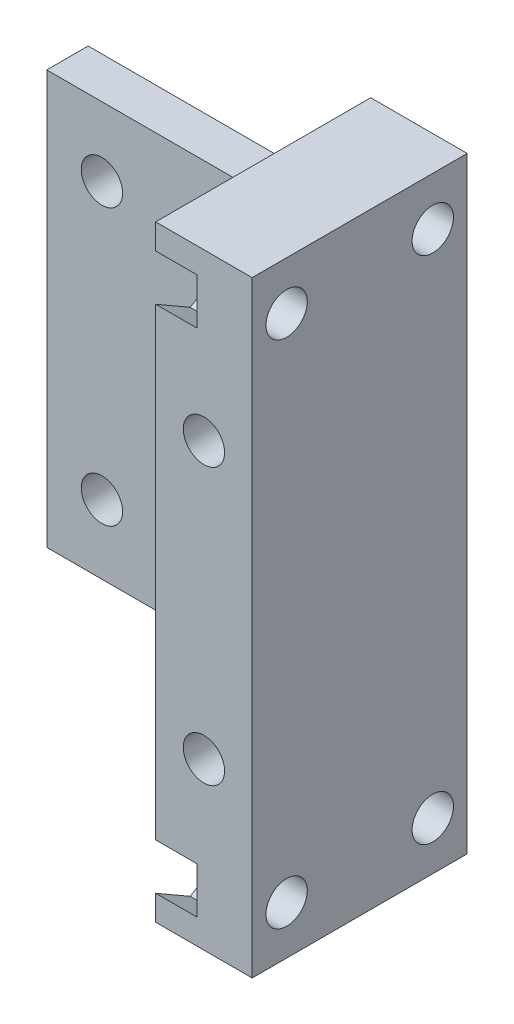
SolidWorks part; units mm, degrees
ref_plane "Front Plane" through (0, 0, 0) normal (0, 0, 1) x (1, 0, 0)
ref_plane "Top Plane" through (0, 0, 0) normal (0, 1, 0) x (1, 0, 0)
ref_plane "Right Plane" through (0, 0, 0) normal (1, 0, 0) x (0, 0, -1)
sketch "Sketch1" plane through (0, 0, 0) normal (0, 0, 1) x (1, 0, 0)
  line L1 (373.5029, -313.2952) -> (346.0029, -313.2952)
  line L2 (373.5029, -313.2952) -> (373.5029, -343.2952)
  line L3 (373.5029, -343.2952) -> (346.0029, -343.2952)
  line L4 (346.0029, -313.2952) -> (346.0029, -343.2952)
  line L8 (373.5029, -313.2952) -> (366.5029, -313.2952)
  line L9 (373.5029, -313.2952) -> (373.5029, -343.2952)
  line L10 (373.5029, -343.2952) -> (366.5029, -343.2952)
  line L11 (366.5029, -313.2952) -> (366.5029, -343.2952)
  circle A1 centre (370.0029, -338.2952) radius 1.5
  circle A2 centre (370.0029, -318.2952) radius 1.5
  circle A4 centre (350.0029, -318.2952) radius 1.5
  circle A5 centre (350.0029, -338.2952) radius 1.5
  point P4 (0, 0)
  point P5 (0, 0)
  point P6 (0, 0)
  point P7 (0, 0)
  point P8 (0, 0)
  point P9 (0, 0)
  point P10 (0, 0)
  point P11 (373.5029, -313.2952)
  point P16 (0, 0)
  dimension "D4" = 3
  dimension "D5" = 3
  dimension "D6" = 3
  dimension "D7" = 3
  dimension "D8" = 20
  dimension "D9" = 20
  dimension "D10" = 20
  dimension "D2" = 5
  dimension "D3" = 7
  dimension "D12" = 5
  dimension "D13" = 4
  dimension "D14" = 3.5
extrude "Boss-Extrude1" add sketch "Sketch1" along normal blind 5 contours L1 L11 L3 L2 A2 A1 | L11 L1 L4 L3 region at (370.0029, -328.2952, 0) region at (356.4, -328.2952, 0)
extrude "Boss-Extrude2" add sketch "Sketch1<3>" along normal blind 15.6 contours L1 L11 L3 L2 A2 A1 region at (370.0029, -328.2952, 0)
sketch "Sketch1<3>" plane through (0, 0, 0) normal (0, 0, 1) x (1, 0, 0) same geometry as "Sketch1"
sketch "Sketch4" plane through (373.5029, 0, 0) normal (1, 0, 0) x (0, 0, -1)
  line L0 (-15.6, -328.2952) -> (0, -328.2952) construction
  line L1 (-15.6, -313.2952) -> (0, -313.2952)
  line L2 (-15.6, -313.2952) -> (-15.6, -306.2952)
  line L3 (-15.6, -306.2952) -> (0, -306.2952)
  line L5 (-15.6, -313.2952) -> (0, -306.2952) construction
  line L6 (-15.6, -306.2952) -> (0, -313.2952) construction
  line L7 (-15.6, -313.2952) -> (-15.6, -343.2952) construction
  line L8 (0, -313.2952) -> (0, -343.2952) construction
  line L9 (-15.6, -309.7952) -> (0, -309.7952) construction
  line L10 (-15.8, -308.2364) -> (-15.8, -311.3541)
  line L11 (-15.8, -311.3541) -> (-13.1, -312.9129)
  line L12 (-13.1, -312.9129) -> (-10.4, -311.3541)
  line L13 (-10.4, -311.3541) -> (-10.4, -308.2364)
  line L14 (-10.4, -308.2364) -> (-13.1, -306.6775)
  line L15 (-13.1, -306.6775) -> (-15.8, -308.2364)
  line L16 (0, -313.2952) -> (0, -306.2952)
  line L23 (-5.2, -308.2364) -> (-5.2, -311.3541)
  line L24 (-5.2, -311.3541) -> (-2.5, -312.9129)
  line L25 (-2.5, -312.9129) -> (0.2, -311.3541)
  line L26 (0.2, -311.3541) -> (0.2, -308.2364)
  line L27 (0.2, -308.2364) -> (-2.5, -306.6775)
  line L28 (-2.5, -306.6775) -> (-5.2, -308.2364)
  circle A0 centre (-13.1, -309.7952) radius 1.5
  circle A1 centre (-13.1, -309.7952) radius 2.7 construction
  circle A2 centre (-2.5, -309.7952) radius 1.5
  circle A3 centre (-2.5, -309.7952) radius 2.7 construction
  point P4 (-13.1, -309.7952)
  point P14 (0, 0)
  point P22 (0, 0)
  point P23 (0.2, -311.3175)
  point P34 (-8.9277, -311.3175)
  line M5 (0, -313.2952) -> (-15.6, -313.2952)
  dimension "D2" = 3
  dimension "D4" = 3
  dimension "D1" = 5.4
  dimension "D3" = 5.4
  dimension "D5" = 7
  dimension "D6" = 2.5
  dimension "D7" = 10.6
extrude "Boss-Extrude3" add sketch "Sketch4" against normal blind 4 contours L28 L27 L16 L3 L2 L15 L14 L13 L12 L11 L25 L24 L23 M5 | L27 L28 L23 L24 L25 L16 A2 | L14 L15 L2 L11 L12 L13 A0 region at (373.5029, -309.7952, 7.8) region at (373.5029, -309.7952, 15.5188) region at (373.5029, -312.1209, 1.2906)
extrude "Boss-Extrude4" add sketch "Sketch4<3>" against normal blind 3 from surface contours L28 L27 L16 L3 L2 L15 L14 L13 L12 L11 L25 L24 L23 M5 region at (373.5029, -309.7952, 7.8) starting at face at (369.5029, -309.7952, 7.8)
sketch "Sketch4<3>" plane through (373.5029, 0, 0) normal (1, 0, 0) x (0, 0, -1) same geometry as "Sketch4"
ref_plane "Plane1" through (0, -328.2952, 0) normal (0, 1, 0) x (1, 0, 0)
mirror "Mirror1" about plane through (0, -328.2952, 0) normal (0, 1, 0) of "Boss-Extrude3", "Boss-Extrude4"
sketch "Sketch5" plane through (0, 0, 5) normal (0, 0, 1) x (1, 0, 0)
  line L1 (346.0029, -313.2952) -> (366.5029, -313.2952)
  line L2 (346.0029, -313.2952) -> (346.0029, -343.2952)
  line L3 (346.0029, -343.2952) -> (366.5029, -343.2952)
  line L4 (366.5029, -313.2952) -> (366.5029, -343.2952)
  line L5 (346.0029, -313.2952) -> (366.5029, -343.2952) construction
  line L6 (346.0029, -343.2952) -> (366.5029, -313.2952) construction
  point P4 (356.2529, -328.2952)
extrude "Cut-Extrude1" cut sketch "Sketch5" against normal blind 2
